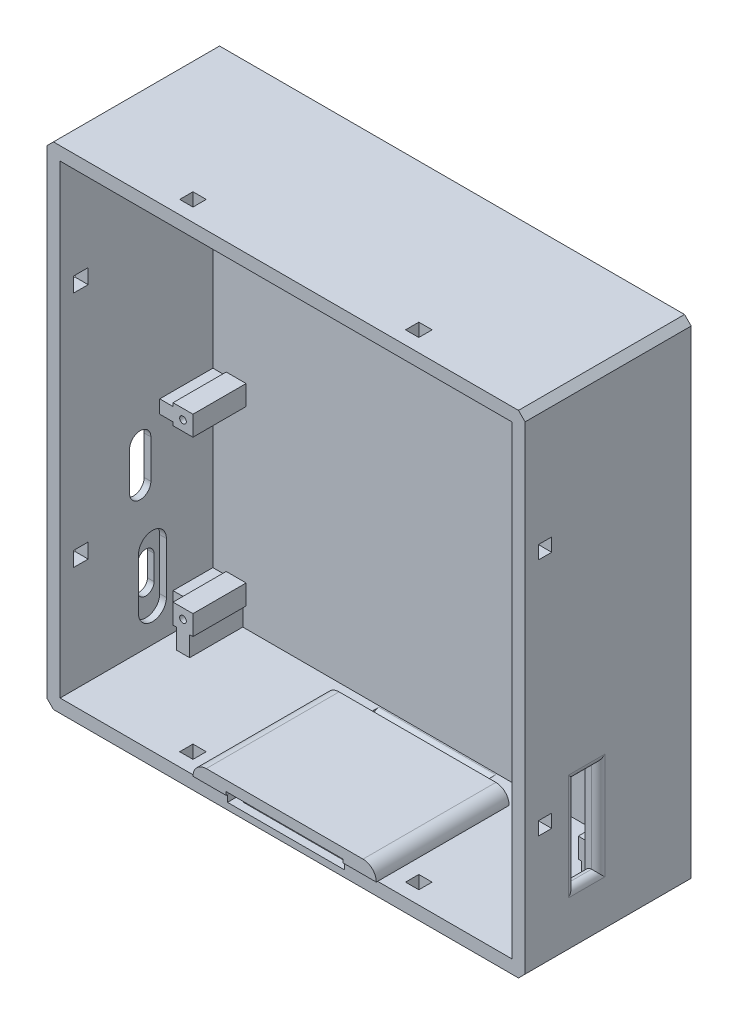
SolidWorks part; units mm, degrees
ref_plane "前视基准面" through (0, 0, 0) normal (0, 0, 1) x (1, 0, 0)
ref_plane "上视基准面" through (0, 0, 0) normal (0, 1, 0) x (1, 0, 0)
ref_plane "右视基准面" through (0, 0, 0) normal (1, 0, 0) x (0, 0, -1)
sketch "草图1" plane through (0, 0, 0) normal (0, 0, 1) x (1, 0, 0)
  line L1 (-21.8087, 48.178) -> (50.1913, 48.178)
  line L2 (-21.8087, 48.178) -> (-21.8087, -25.822)
  line L3 (-21.8087, -25.822) -> (50.1913, -25.822)
  line L4 (50.1913, 48.178) -> (50.1913, -25.822)
  dimension "D1" = 74
  dimension "D2" = 72
extrude "凸台-拉伸1" add sketch "草图1" along normal blind 25
sketch "草图2" plane through (0, 0, 25) normal (0, 0, 1) x (1, 0, 0)
  line L0 (50.1913, 48.178) -> (-21.8087, 48.178) construction
  line L1 (-19.8087, 46.178) -> (48.1913, 46.178)
  line L2 (-19.8087, 46.178) -> (-19.8087, -23.822)
  line L3 (-19.8087, -23.822) -> (48.1913, -23.822)
  line L4 (48.1913, 46.178) -> (48.1913, -23.822)
  line L5 (-21.8087, -25.822) -> (50.1913, -25.822) construction
  line L6 (50.1913, -25.822) -> (50.1913, 48.178) construction
  line L7 (-21.8087, 48.178) -> (-21.8087, -25.822) construction
  dimension "D1" = 2
  dimension "D2" = 2
  dimension "D3" = 2
  dimension "D4" = 2
extrude "切除-拉伸1" cut sketch "草图2" against normal blind 23
sketch "草图3" plane through (0, 46.178, 0) normal (0, -1, 0) x (1, 0, 0)
  line L0 (48.1913, 25) -> (-19.8087, 25) construction
  line L1 (-3.8087, 23) -> (-1.8087, 23)
  line L2 (-3.8087, 23) -> (-3.8087, 21)
  line L3 (-3.8087, 21) -> (-1.8087, 21)
  line L4 (-1.8087, 23) -> (-1.8087, 21)
  line L5 (30.1913, 23) -> (32.1913, 23)
  line L6 (30.1913, 23) -> (30.1913, 21)
  line L7 (30.1913, 21) -> (32.1913, 21)
  line L8 (32.1913, 23) -> (32.1913, 21)
  line L9 (48.1913, 2) -> (48.1913, 25) construction
  line L10 (-19.8087, 2) -> (-19.8087, 25) construction
  dimension "D1" = 2
  dimension "D2" = 2
  dimension "D3" = 2
  dimension "D4" = 16
  dimension "D5" = 16
extrude "切除-拉伸2" cut sketch "草图3" against normal up to next
sketch "草图4" plane through (48.1913, 0, 0) normal (-1, 0, 0) x (0, 0, 1)
  line L1 (23, 30.178) -> (21, 30.178)
  line L2 (23, 30.178) -> (23, 28.178)
  line L3 (23, 28.178) -> (21, 28.178)
  line L4 (21, 30.178) -> (21, 28.178)
  line L5 (23, -5.822) -> (21, -5.822)
  line L6 (23, -5.822) -> (23, -7.822)
  line L7 (23, -7.822) -> (21, -7.822)
  line L8 (21, -5.822) -> (21, -7.822)
  line L10 (25, -23.822) -> (25, 46.178) construction
  line L11 (2, 46.178) -> (25, 46.178) construction
  line L12 (2, -23.822) -> (25, -23.822) construction
  dimension "D1" = 2
  dimension "D2" = 2
  dimension "D3" = 2
  dimension "D4" = 16
  dimension "D5" = 16
sketch "草图5" plane through (0, -23.822, 0) normal (0, 1, 0) x (1, 0, 0)
  line L0 (-19.8087, -25) -> (48.1913, -25) construction
  line L1 (32.1913, -23) -> (30.1913, -23)
  line L2 (32.1913, -23) -> (32.1913, -21)
  line L3 (32.1913, -21) -> (30.1913, -21)
  line L4 (30.1913, -23) -> (30.1913, -21)
  line L5 (-1.8087, -23) -> (-3.8087, -23)
  line L6 (-1.8087, -23) -> (-1.8087, -21)
  line L7 (-1.8087, -21) -> (-3.8087, -21)
  line L8 (-3.8087, -23) -> (-3.8087, -21)
  line L9 (48.1913, -2) -> (48.1913, -25) construction
  line L10 (-19.8087, -2) -> (-19.8087, -25) construction
  dimension "D1" = 2
  dimension "D2" = 2
  dimension "D3" = 16
  dimension "D4" = 16
sketch "草图6" plane through (-19.8087, 0, 0) normal (1, 0, 0) x (0, 0, -1)
  line L0 (-25, 46.178) -> (-25, -23.822) construction
  line L1 (-23, 30.178) -> (-20.7747, 30.178)
  line L2 (-23, 30.178) -> (-23, 27.9527)
  line L3 (-23, 27.9527) -> (-20.7747, 27.9527)
  line L4 (-20.7747, 30.178) -> (-20.7747, 27.9527)
  line L5 (-23, -5.5967) -> (-20.7747, -5.5967)
  line L6 (-23, -5.5967) -> (-23, -7.822)
  line L7 (-23, -7.822) -> (-20.7747, -7.822)
  line L8 (-20.7747, -5.5967) -> (-20.7747, -7.822)
  line L9 (-2, -23.822) -> (-25, -23.822) construction
  line L10 (-2, 46.178) -> (-25, 46.178) construction
  dimension "D1" = 2
  dimension "D2" = 16
  dimension "D3" = 16
extrude "切除-拉伸3" cut sketch "草图4" against normal up to next
extrude "切除-拉伸4" cut sketch "草图5" against normal up to next
extrude "切除-拉伸5" cut sketch "草图6" against normal up to next
sketch "草图7" plane through (0, 0, 2) normal (0, 0, 1) x (1, 0, 0)
  line L1 (-17.8087, -20.822) -> (-14.8087, -20.822)
  line L2 (-17.8087, -20.822) -> (-17.8087, -17.822)
  line L3 (-17.8087, -17.822) -> (-14.8087, -17.822)
  line L4 (-14.8087, -20.822) -> (-14.8087, -17.822)
  line L5 (-17.8087, 5.178) -> (-14.8087, 5.178)
  line L6 (-17.8087, 5.178) -> (-17.8087, 8.178)
  line L7 (-17.8087, 8.178) -> (-14.8087, 8.178)
  line L8 (-14.8087, 5.178) -> (-14.8087, 8.178)
  line L9 (43.1913, -20.822) -> (46.1913, -20.822)
  line L10 (43.1913, -20.822) -> (43.1913, -17.822)
  line L11 (43.1913, -17.822) -> (46.1913, -17.822)
  line L12 (46.1913, -20.822) -> (46.1913, -17.822)
  line L13 (43.1913, 5.178) -> (46.1913, 5.178)
  line L14 (43.1913, 5.178) -> (43.1913, 8.178)
  line L15 (43.1913, 8.178) -> (46.1913, 8.178)
  line L16 (46.1913, 5.178) -> (46.1913, 8.178)
  line L18 (48.1913, -23.822) -> (48.1913, 46.178) construction
  line L19 (-19.8087, 46.178) -> (-19.8087, -23.822) construction
  line L20 (-19.8087, -23.822) -> (48.1913, -23.822) construction
  dimension "D1" = 3
  dimension "D2" = 23
  dimension "D3" = 2
  dimension "D4" = 3
  dimension "D5" = 2
extrude "凸台-拉伸2" add sketch "草图7" along normal blind 8
sketch "草图10" plane through (0, 0, 10) normal (0, 0, 1) x (1, 0, 0)
  line L0 (-17.8087, -17.822) -> (-14.8087, -20.822) construction
  line L1 (-14.8087, -20.822) -> (-14.8087, -17.822) construction
  line L2 (-14.8087, -17.822) -> (-17.8087, -20.822) construction
  line L3 (43.1913, 8.178) -> (46.1913, 5.178) construction
  line L4 (46.1913, 5.178) -> (46.1913, 8.178) construction
  line L5 (46.1913, 8.178) -> (43.1913, 5.178) construction
  circle A0 centre (44.6913, 6.678) radius 0.5
  circle A1 centre (44.6913, -19.322) radius 0.5
  circle A2 centre (-16.3087, -19.322) radius 0.5
  circle A3 centre (-16.3087, 6.678) radius 0.5
  point P17 (-16.3087, -19.322)
  point P26 (44.6913, 6.678)
  dimension "D1" = 1
extrude "切除-拉伸6" cut sketch "草图10" against normal blind 3
sketch "草图12" plane through (-17.8087, 0, 0) normal (-1, 0, 0) x (0, 0, 1)
  line L1 (2, -18.322) -> (8, -18.322)
  line L2 (2, -18.322) -> (2, -20.322)
  line L3 (2, -20.322) -> (8, -20.322)
  line L4 (8, -18.322) -> (8, -20.322)
  line L5 (2, -17.822) -> (2, -20.822) construction
  line L6 (10, -17.822) -> (10, -20.822) construction
  line L7 (2, 7.678) -> (10, 7.678)
  line L8 (2, 7.678) -> (2, 5.678)
  line L9 (2, 5.678) -> (10, 5.678)
  line L10 (10, 7.678) -> (10, 5.678)
  line L11 (10, 5.178) -> (2, 5.178) construction
  line L12 (10, 8.178) -> (10, 5.178) construction
  line L13 (2, 8.178) -> (2, 5.178) construction
  line L14 (10, -20.822) -> (2, -20.822) construction
  dimension "D1" = 0.5
  dimension "D2" = 2
  dimension "D3" = 2
  dimension "D4" = 0.5
  dimension "D5" = 2
extrude "凸台-拉伸3" add sketch "草图12" along normal up to next
sketch "草图13" plane through (46.1913, 0, 0) normal (1, 0, 0) x (0, 0, -1)
  line L1 (-10, 7.678) -> (-2, 7.678)
  line L2 (-10, 7.678) -> (-10, 5.678)
  line L3 (-10, 5.678) -> (-2, 5.678)
  line L4 (-2, 7.678) -> (-2, 5.678)
  line L5 (-10, 5.178) -> (-10, 8.178) construction
  line L6 (-2, 5.178) -> (-2, 8.178) construction
  line L7 (-10, 5.178) -> (-2, 5.178) construction
  line L8 (-10, -20.822) -> (-10, -17.822) construction
  line L9 (-10, -18.322) -> (-2, -18.322)
  line L10 (-10, -18.322) -> (-10, -20.322)
  line L11 (-10, -20.322) -> (-2, -20.322)
  line L12 (-2, -18.322) -> (-2, -20.322)
  line L13 (-2, -20.822) -> (-2, -17.822) construction
  line L14 (-10, -20.822) -> (-2, -20.822) construction
  point P20 (-6, -20.822)
  dimension "D1" = 2
  dimension "D2" = 0.5
  dimension "D3" = 2
  dimension "D4" = 0.5
extrude "凸台-拉伸4" add sketch "草图13" along normal up to next
sketch "草图14" plane through (0, -20.822, 0) normal (0, -1, 0) x (1, 0, 0)
  line L0 (-17.8087, 10) -> (-14.8087, 10) construction
  line L1 (-17.3087, 10) -> (-15.3087, 10)
  line L2 (-17.3087, 10) -> (-17.3087, 2)
  line L3 (-17.3087, 2) -> (-15.3087, 2)
  line L4 (-15.3087, 10) -> (-15.3087, 2)
  line L5 (43.6913, 10) -> (45.6913, 10)
  line L6 (43.6913, 10) -> (43.6913, 4.0576)
  line L7 (43.6913, 4.0576) -> (45.6913, 4.0576)
  line L8 (45.6913, 10) -> (45.6913, 4.0576)
  line L9 (-17.8087, 2) -> (-14.8087, 2) construction
  line L11 (-17.8087, 10) -> (-17.8087, 2) construction
  line L13 (43.1913, 10) -> (43.1913, 2) construction
  dimension "D1" = 2
  dimension "D2" = 2
  dimension "D3" = 0.5
  dimension "D4" = 0.5
extrude "凸台-拉伸5" add sketch "草图14" along normal up to next
sketch "草图15" plane through (-21.8087, 0, 0) normal (-1, 0, 0) x (0, 0, 1)
  line L0 (12.94, 3.798) -> (12.94, -2.402) construction
  line L1 (16.54, 3.798) -> (16.54, -2.402)
  line L2 (9.34, 3.798) -> (9.34, -2.402)
  line L4 (25, -25.822) -> (0, -25.822) construction
  line L5 (0, 48.178) -> (0, -25.822) construction
  arc A0 (16.54, 3.798) -> (9.34, 3.798) centre (12.94, 3.798) ccw
  arc A1 (9.34, -2.402) -> (16.54, -2.402) centre (12.94, -2.402) ccw
  point P0 (12.94, -6.002)
  point P3 (12.94, 0.698)
  point P8 (9.34, 0.698)
  dimension "D3" = 19.82
  dimension "D1" = 6.2
  dimension "D2" = 7.2
  dimension "D4" = 9.34
extrude "切除-拉伸8" cut sketch "草图15" against normal blind 1
sketch "草图18" plane through (-20.8087, 0, 0) normal (-1, 0, 0) x (0, 0, 1)
  line L0 (12.94, 3.398) -> (12.94, -2.402) construction
  line L3 (14.54, 3.398) -> (14.54, -2.402)
  line L4 (11.34, 3.398) -> (11.34, -2.402)
  line L5 (16.54, -2.402) -> (16.54, 3.798) construction
  arc A2 (9.34, -2.402) -> (16.54, -2.402) centre (12.94, -2.402) ccw construction
  arc A3 (14.54, 3.398) -> (11.34, 3.398) centre (12.94, 3.398) ccw
  arc A4 (11.34, -2.402) -> (14.54, -2.402) centre (12.94, -2.402) ccw
  point P2 (12.94, 0.498)
  point P7 (12.94, 4.998)
  point P8 (12.94, -4.002)
  point P12 (12.94, -6.002)
  dimension "D1" = 3.2
  dimension "D2" = 9
  dimension "D3" = 2
  dimension "D4" = 2
extrude "切除-拉伸9" cut sketch "草图18" against normal blind 1
sketch "草图19" plane through (-19.8087, 0, 0) normal (1, 0, 0) x (0, 0, -1)
  line L0 (-11.1, -11.022) -> (-11.1, -18.722) construction
  line L1 (-9, -11.022) -> (-9, -18.722)
  line L2 (-13.2, -11.022) -> (-13.2, -18.722)
  line L3 (-2, 5.678) -> (-2, -18.322) construction
  line L4 (-2, -23.822) -> (-25, -23.822) construction
  arc A0 (-9, -11.022) -> (-13.2, -11.022) centre (-11.1, -11.022) ccw
  arc A1 (-13.2, -18.722) -> (-9, -18.722) centre (-11.1, -18.722) ccw
  point P2 (-11.1, -14.872)
  point P9 (-11.1, -20.822)
  dimension "D1" = 7.7
  dimension "D2" = 4.2
  dimension "D3" = 7
  dimension "D4" = 3
extrude "切除-拉伸10" cut sketch "草图19" against normal blind 1 contours L1 A1 L2 A0
sketch "草图20" plane through (-20.8087, 0, 0) normal (1, 0, 0) x (0, 0, -1)
  line L0 (-12.35, -16.722) -> (-12.35, -13.2168)
  line L1 (-9.85, -13.0402) -> (-9.85, -16.722)
  line L3 (-9, -11.022) -> (-9, -18.722) construction
  arc A0 (-9.85, -13.0402) -> (-12.35, -13.2168) centre (-11.1005, -13.122) ccw
  arc A1 (-12.35, -16.722) -> (-9.85, -16.722) centre (-11.1, -16.722) ccw
  arc A3 (-13.2, -18.722) -> (-9, -18.722) centre (-11.1, -18.722) ccw construction
  dimension "D4" = 0.85
  dimension "D5" = 1.25
  dimension "D6" = 1.2531
  dimension "D1" = 2.5
  dimension "D2" = 3.6
  dimension "D3" = 2
extrude "切除-拉伸11" cut sketch "草图20" against normal blind 1
sketch "草图21" plane through (50.1913, 0, 0) normal (1, 0, 0) x (0, 0, -1)
  line L0 (0, -25.822) -> (0, 48.178) construction
  line L1 (-17.5, -17.142) -> (-14, -17.142)
  line L2 (-17.5, -17.142) -> (-17.5, -3.142)
  line L3 (-17.5, -3.142) -> (-14, -3.142)
  line L4 (-14, -17.142) -> (-14, -3.142)
  line L5 (-25, -25.822) -> (0, -25.822) construction
  dimension "D1" = 17.5
  dimension "D2" = 3.5
  dimension "D3" = 8.68
  dimension "D4" = 14
extrude "切除-拉伸12" cut sketch "草图21" against normal up to next
sketch "草图22" plane through (0, -23.822, 0) normal (0, 1, 0) x (1, 0, 0)
  line L0 (48.1913, -2) -> (48.1913, -25) construction
  line L1 (5.3913, -25) -> (22.9913, -25)
  line L2 (5.3913, -25) -> (5.3913, -3.2)
  line L3 (5.3913, -3.2) -> (22.9913, -3.2)
  line L4 (22.9913, -25) -> (22.9913, -3.2)
  line L6 (-19.8087, -25) -> (48.1913, -25) construction
  dimension "D1" = 42.8
  dimension "D2" = 17.6
  dimension "D3" = 21.8
extrude "切除-拉伸13" cut sketch "草图22" against normal blind 1 contours L2 L1 L4 L3
sketch "草图24" plane through (0, -24.822, 0) normal (0, 1, 0) x (1, 0, 0)
  line L0 (5.3913, -25) -> (5.3913, -3.2) construction
  line L1 (6.5913, -23.8) -> (21.7913, -23.8)
  line L2 (6.5913, -23.8) -> (6.5913, -8.6)
  line L3 (6.5913, -8.6) -> (21.7913, -8.6)
  line L4 (21.7913, -23.8) -> (21.7913, -8.6)
  line L6 (5.3913, -25) -> (22.9913, -25) construction
  dimension "D1" = 15.2
  dimension "D2" = 15.2
  dimension "D3" = 1.2
  dimension "D4" = 1.2
extrude "切除-拉伸14" cut sketch "草图24" against normal blind 1
sketch "草图27" plane through (0, -23.822, 0) normal (0, 1, 0) x (1, 0, 0)
  line L0 (5.3913, -25) -> (5.3913, -3.2) construction
  line L1 (0.3913, -25.2) -> (27.9913, -25.2)
  line L2 (0.3913, -25.2) -> (0.3913, -5.2)
  line L3 (0.3913, -5.2) -> (27.9913, -5.2)
  line L4 (27.9913, -25.2) -> (27.9913, -5.2)
  line L5 (22.9913, -25) -> (22.9913, -3.2) construction
  line L6 (5.3913, -3.2) -> (22.9913, -3.2) construction
  dimension "D1" = 5
  dimension "D2" = 5
  dimension "D3" = 20
  dimension "D4" = 2
extrude "凸台-拉伸6" add sketch "草图27" along normal blind 2 contours L2 L1 L4 L3
sketch "草图28" plane through (0, 0, 25.2) normal (0, 0, 1) x (1, 0, 0)
  line L0 (0.3913, -23.822) -> (27.9913, -23.822) construction
  line L1 (5.3889, -23.822) -> (22.9913, -23.822)
  line L2 (5.3889, -23.822) -> (5.3889, -23.322)
  line L3 (5.3889, -23.322) -> (22.9913, -23.322)
  line L4 (22.9913, -23.822) -> (22.9913, -23.322)
  line L5 (22.9913, -24.822) -> (22.9913, -23.822) construction
  dimension "D1" = 0.5
extrude "切除-拉伸16" cut sketch "草图28" against normal up to next contours L2 L1 L4 L3
fillet "圆角1" radius 1 1 edges at (14.1913, -23.822, 3.2)
fillet "圆角2" radius 2 2 edges at (0.3913, -21.822, 15.2) (27.9913, -21.822, 15.2)
chamfer "倒角1" distance 1 angle 45 4 edges at (50.1913, -25.822, 12.5) (50.1913, 48.178, 12.5) (-21.8087, -25.822, 12.5) (-21.8087, 48.178, 12.5)
fillet "圆角3" radius 1 2 edges at (48.1913, -17.142, 15.75) (48.1913, -3.142, 15.75)
fillet "圆角4" radius 1 4 edges at (50.1913, -10.142, 17.5) (50.1913, -10.142, 14) (50.1913, -17.142, 15.75) (50.1913, -3.142, 15.75)
chamfer "倒角3" distance 0.5 angle 45 4 edges at (6.5913, -25.822, 16.2) (14.1913, -25.822, 8.6) (21.7913, -25.822, 16.2) (14.1913, -25.822, 23.8)
